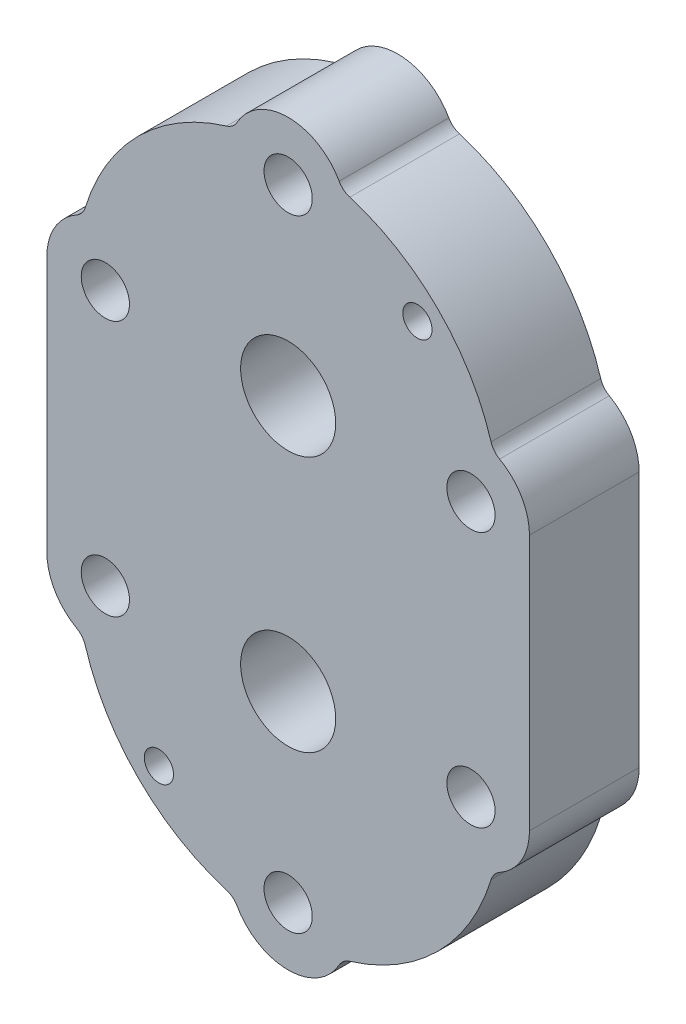
SolidWorks part; units mm, degrees
ref_plane "前视基准面" through (0, 0, 0) normal (0, 0, 1) x (1, 0, 0)
ref_plane "上视基准面" through (0, 0, 0) normal (0, 1, 0) x (1, 0, 0)
ref_plane "右视基准面" through (0, 0, 0) normal (1, 0, 0) x (0, 0, -1)
sketch "草图3" plane through (0, 0, 0) normal (0, 0, 1) x (1, 0, 0)
  line L0 (0, -17.5) -> (0, 17.5) construction
  line L1 (0, -63.0031) -> (0, 63.0031) construction
  line L2 (-14, -17.5) -> (-14, 17.5)
  line L3 (14, -17.5) -> (14, 17.5)
  line L4 (-25, -17.5) -> (-25, 17.5) construction
  line L5 (25, -17.5) -> (25, 17.5) construction
  line L6 (0, 17.5) -> (28.2843, 45.7843) construction
  line L7 (0, -17.5) -> (-28.2843, -45.7843) construction
  line L8 (0, 55.1294) -> (0, -55.2393) construction
  line L9 (-33, 17.5) -> (-33, -17.5)
  line L10 (33, 17.5) -> (33, -17.5)
  line L11 (29, -17.5) -> (29, 17.5) construction
  line L12 (-29, -17.5) -> (-29, 17.5) construction
  arc A0 (-14, -17.5) -> (14, -17.5) centre (0, -17.5) ccw
  arc A1 (14, 17.5) -> (-14, 17.5) centre (0, 17.5) ccw
  arc A2 (25, 17.5) -> (-25, 17.5) centre (0, 17.5) ccw construction
  arc A3 (-25, -17.5) -> (25, -17.5) centre (0, -17.5) ccw construction
  arc A4 (27.7479, 25.9292) -> (8.4292, 45.2479) centre (0, 17.5) ccw
  arc A5 (-27.7479, -25.9292) -> (-8.4292, -45.2479) centre (0, -17.5) ccw
  arc A6 (6.9759, 46.4162) -> (-6.9759, 46.4162) centre (0, 42.5) ccw
  arc A7 (-28.9162, 24.4759) -> (-33, 17.5) centre (-25, 17.5) ccw
  arc A8 (-32.877, -16.1024) -> (-28.9162, -24.4759) centre (-25, -17.5) ccw
  arc A9 (28.9162, 24.4759) -> (33, 17.5) centre (25, 17.5) cw
  arc A10 (8.4292, -45.2479) -> (27.7479, -25.9292) centre (0, -17.5) ccw
  arc A11 (-6.9759, -46.4162) -> (6.9759, -46.4162) centre (0, -42.5) ccw
  arc A12 (-8.4292, 45.2479) -> (-27.7479, 25.9292) centre (0, 17.5) ccw
  arc A13 (29, 17.5) -> (-29, 17.5) centre (0, 17.5) ccw construction
  arc A14 (-29, -17.5) -> (29, -17.5) centre (0, -17.5) ccw construction
  arc A15 (33, -17.5) -> (28.9162, -24.4759) centre (25, -17.5) cw
  arc A16 (6.9759, -46.4162) -> (8.4292, -45.2479) centre (9.1559, -47.64) cw
  arc A17 (-6.9759, -46.4162) -> (-8.4292, -45.2479) centre (-9.1559, -47.64) ccw
  arc A18 (27.7479, 25.9292) -> (28.9162, 24.4759) centre (30.14, 26.6559) ccw
  arc A19 (27.7479, -25.9292) -> (28.9162, -24.4759) centre (30.14, -26.6559) cw
  arc A20 (-27.7479, -25.9292) -> (-28.9162, -24.4759) centre (-30.14, -26.6559) ccw
  arc A21 (-28.9162, 24.4759) -> (-27.7479, 25.9292) centre (-30.14, 26.6559) ccw
  arc A22 (6.9759, 46.4162) -> (8.4292, 45.2479) centre (9.1559, 47.64) ccw
  arc A23 (-8.4292, 45.2479) -> (-6.9759, 46.4162) centre (-9.1559, 47.64) ccw
  circle A24 centre (-17.6777, -35.1777) radius 2
  circle A25 centre (17.6777, 35.1777) radius 2
  point P5 (0, 0)
  point P44 (7.3999, -45.54)
  point P59 (-7.3999, 45.54)
  point P61 (0, 42.5)
  dimension "D5" = 16
  dimension "D6" = 16
  dimension "D7" = 2.5
  dimension "D8" = 16
  dimension "D9" = 4
  dimension "D10" = 4
  dimension "D1" = 35
  dimension "D2" = 28
  dimension "D11" = 45
  dimension "D12" = 40
  dimension "D13" = 40
  dimension "D3" = 11
  dimension "D4" = 15
extrude "凸台-拉伸4" add sketch "草图3" along normal blind 15 contours A23 A12 A21 A7 L9 A8 A20 A5 A17 A11 A16 A10 A19 A15 L10 A9 A18 A4 A22 A6 A1 L3 A0 L2 | L3 A1 L2 A0 region at (0, 0, 0) region at (-30.8627, 20.9321, 0)
extrude "凸台-拉伸5" add sketch "草图3<6>" against normal blind 7 contours L3 A1 L2 A0 region at (0, 0, 0)
sketch "草图3<6>" plane through (0, 0, 0) normal (0, 0, 1) x (1, 0, 0) same geometry as "草图3"
hole_wizard "Ø13.0 (13) 直径孔2" positions "3D草图7" profile "草图11" hole size "Ø13.0" standard "GB"
sketch3d "3D草图7"
  line L0 (0, 17.5, 15) -> (0, 17.5, 0) construction
  line L1 (0, -17.5, 15) -> (0, -17.5, 0) construction
  point P0 (0, 17.5, 15)
  point P4 (0, -17.5, 15)
sketch "草图11" plane through (0, 17.5, 15) normal (1, 0, 0) x (0, -1, 0)
  line L0 (0, 0) -> (0, 18.9056)
  line L1 (0, 18.9056) -> (6.5, 15)
  line L2 (6.5, 15) -> (6.5, 0)
  line L5 (6.5, 0) -> (0, 0)
  line L10 (0, 18.9056) -> (-6.5, 15) construction
  line L11 (0, -6.35) -> (0, 107.95) construction
  dimension "孔直径" = 13
  dimension "孔深度" = 15
  dimension "导头角度" = 118
sketch "草图16" plane through (0, 0, 0) normal (0, 0, -1) x (-1, 0, 0)
  point P0 (0, 42.5)
  point P1 (-25, 17.5)
  point P3 (25, 17.5)
  point P5 (-25, -17.5)
  point P7 (25, -17.5)
  point P9 (0, -42.5)
hole_wizard "打孔尺寸(%根据)开槽圆柱头螺钉的类型2" positions "草图18" profile "草图19" counterbore size "M6" standard "GB"
sketch "草图18" plane through (0, 0, 0) normal (0, 0, -1) x (-1, 0, 0)
  point P0 (0, 42.5)
  point P3 (-25, 17.5)
  point P6 (25, 17.5)
  point P9 (-25, -17.5)
  point P12 (25, -17.5)
  point P15 (0, -42.5)
sketch "草图19" plane through (0, 42.5, 0) normal (1, 0, 0) x (0, 1, 0)
  line L0 (0, 0) -> (0, 16.9828)
  line L1 (0, 16.9828) -> (3.3, 15)
  line L2 (3.3, 15) -> (3.3, 6.8)
  line L3 (3.3, 6.8) -> (5.5, 6.8)
  line L4 (5.5, 6.8) -> (5.5, 0)
  line L5 (5.5, 0) -> (0, 0)
  line L10 (0, 16.9828) -> (-3.3, 15) construction
  line L11 (0, -6.35) -> (0, 107.95) construction
  dimension "孔直径" = 6.6
  dimension "孔深度" = 15
  dimension "柱形沉头孔直径" = 11
  dimension "柱形沉头孔深度" = 6.8
  dimension "导头角度" = 118
fillet "圆角1" radius 1 8 edges at (0, -31.5, -7) (-14, 0, -7) (0, 31.5, -7) (14, 0, -7) (0, 31.5, 0) (-14, 0, 0) (0, -31.5, 0) (14, 0, 0)
